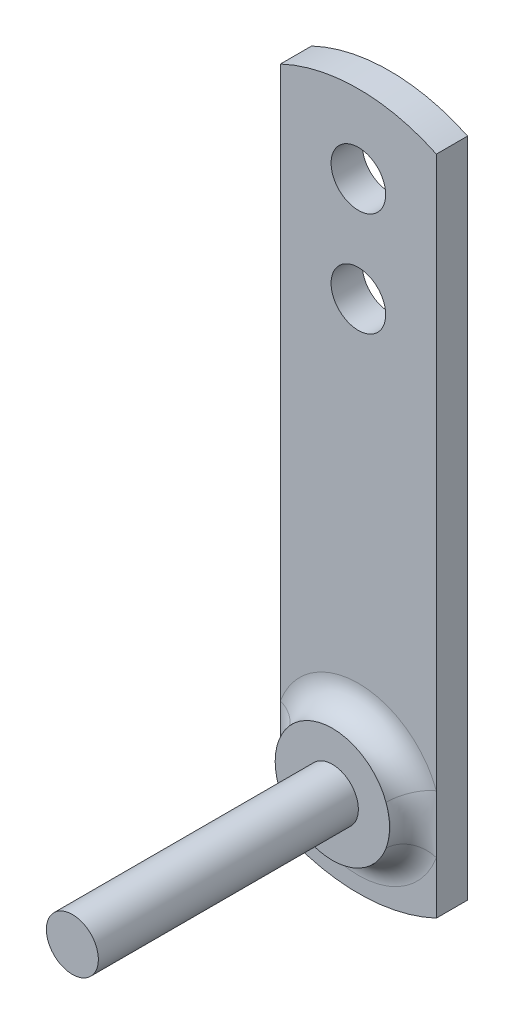
SolidWorks part; units mm, degrees
ref_plane "Přední rovina" through (0, 0, 0) normal (0, 0, 1) x (1, 0, 0)
ref_plane "Horní rovina" through (0, 0, 0) normal (0, 1, 0) x (1, 0, 0)
ref_plane "Pravá rovina" through (0, 0, 0) normal (1, 0, 0) x (0, 0, -1)
sketch "Skica1" plane through (0, 0, 0) normal (0, 0, 1) x (1, 0, 0)
  line L0 (0, 111.8864) -> (0, -120.4049) construction
  line L1 (-121.968, 0) -> (-14.1774, 0) construction
  line L2 (17.5, 0) -> (124.0838, 0) construction
  line L4 (-17.5, -62.3109) -> (-17.5, 62.3109)
  line L6 (17.5, -62.3109) -> (17.5, 62.3109)
  line L7 (-16.4301, -62.9039) -> (16.4301, 62.9039) construction
  line L8 (-16.4301, 62.9039) -> (16.4301, -62.9039) construction
  circle A0 centre (0, 52) radius 5.25
  circle A1 centre (0, 32) radius 5.25
  arc A4 (17.5, 62.3109) -> (-17.5, 62.3109) centre (0, 32) ccw
  arc A5 (-0.7813, -2.9913) -> (0.7813, -2.9913) centre (0, 32) ccw
  arc A6 (0.7813, 2.9913) -> (-0.7813, 2.9913) centre (0, -32) ccw
  arc A8 (-17.5, -62.3109) -> (17.5, -62.3109) centre (0, -32) ccw
  point P5 (0, -48)
  point P7 (0, 0)
  dimension "D3" = 10.5
  dimension "D5" = 80
  dimension "D6" = 100
extrude "Přidat vysunutím1" add sketch "Skica1" along normal blind 6 contours L4 A8 L6 A4 A0 A1 region at (0, -1.6491, 0)
sketch "Skica2" plane through (0, 0, 6) normal (0, 0, 1) x (1, 0, 0)
  line L0 (0, 71.6064) -> (0, -76.6001) construction
  line L1 (0, -67) -> (27.6233, -67) construction
  circle A0 centre (0, -48) radius 11
  arc A1 (-17.5, -62.3109) -> (17.5, -62.3109) centre (0, -32) ccw construction
  dimension "D1" = 19
  dimension "D2" = 22
extrude "Přidat vysunutím2" add sketch "Skica2" along normal blind 5
sketch "Skica3" plane through (0, 0, 6) normal (0, 0, 1) x (1, 0, 0)
  line L0 (0, 83.1478) -> (0, -107.2128) construction
  line L2 (15, 78.3843) -> (51.875, 78.3843)
  line L3 (15, 78.3843) -> (15, -78.3843)
  line L4 (15, -78.3843) -> (51.875, -78.3843)
  line L5 (51.875, 78.3843) -> (51.875, -78.3843)
  line L6 (15, 78.3843) -> (51.875, -78.3843) construction
  line L7 (15, -78.3843) -> (51.875, 78.3843) construction
  line L8 (-15, 81.3343) -> (-54.825, 81.3343)
  line L9 (-15, 81.3343) -> (-15, -81.3343)
  line L10 (-15, -81.3343) -> (-54.825, -81.3343)
  line L11 (-54.825, 81.3343) -> (-54.825, -81.3343)
  line L12 (-15, 81.3343) -> (-54.825, -81.3343) construction
  line L13 (-15, -81.3343) -> (-54.825, 81.3343) construction
  point P3 (33.4375, 0)
  point P8 (-34.9125, 0)
  dimension "D1" = 15
  dimension "D2" = 15
extrude "Odebrat vysunutím1" cut sketch "Skica3" against normal blind 10
fillet "Zaoblit1" radius 5 1 edges at (11, -48, 6)
sketch "Skica4" plane through (0, 0, 11) normal (0, 0, 1) x (1, 0, 0)
  circle A0 centre (0, -48) radius 5
  dimension "D1" = 10
extrude "Přidat vysunutím3" add sketch "Skica4" along normal blind 50
